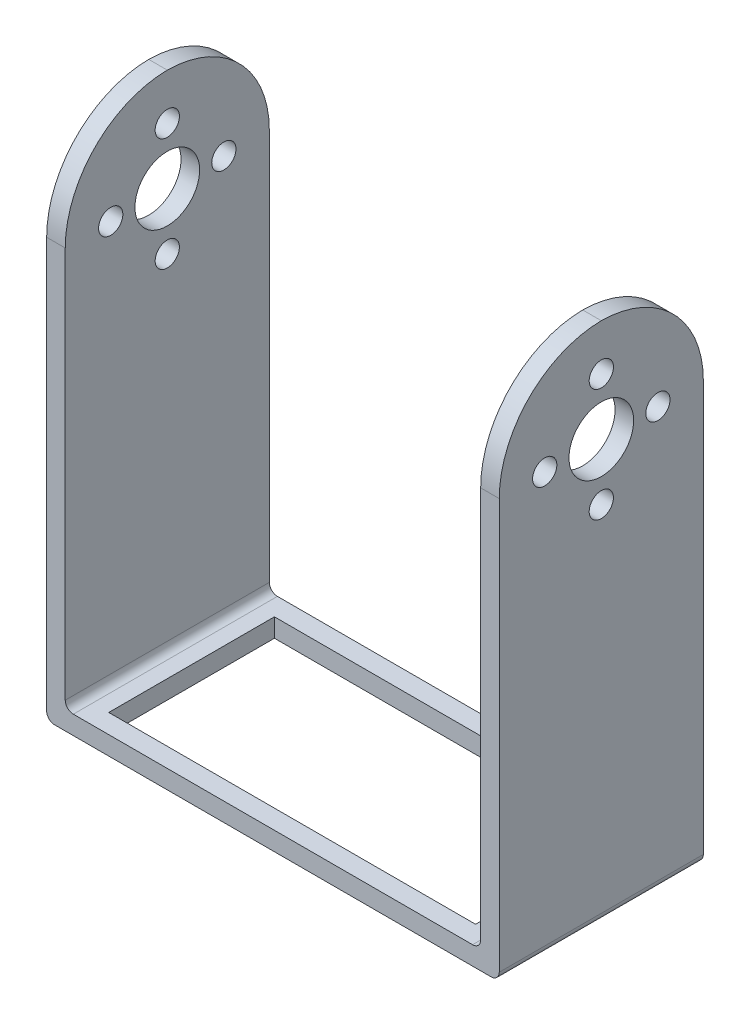
SolidWorks part; units mm, degrees
ref_plane "Front Plane" through (0, 0, 0) normal (0, 0, 1) x (1, 0, 0)
ref_plane "Top Plane" through (0, 0, 0) normal (0, 1, 0) x (1, 0, 0)
ref_plane "Right Plane" through (0, 0, 0) normal (1, 0, 0) x (0, 0, -1)
sketch "Sketch1" plane through (0, 0, 0) normal (0, 0, 1) x (1, 0, 0)
  line L1 (-28, 32.25) -> (28, 32.25)
  line L2 (-28, 32.25) -> (-28, -32.25)
  line L3 (-28, -32.25) -> (28, -32.25)
  line L4 (28, 32.25) -> (28, -32.25)
  line L5 (-28, 32.25) -> (28, -32.25) construction
  line L6 (-28, -32.25) -> (28, 32.25) construction
  point P0 (0, 0)
  dimension "D1" = 56
  dimension "D2" = 64.5
extrude "Boss-Extrude1" add sketch "Sketch1" along normal blind 25.25
sketch "Sketch2" plane through (0, 0, 25.25) normal (0, 0, 1) x (1, 0, 0)
  line L0 (28, 32.25) -> (-28, 32.25) construction
  line L1 (-25.7, 32.25) -> (25.7, 32.25)
  line L2 (-25.7, 32.25) -> (-25.7, -29.95)
  line L3 (-25.7, -29.95) -> (25.7, -29.95)
  line L4 (25.7, 32.25) -> (25.7, -29.95)
  line L5 (-28, 32.25) -> (-28, -32.25) construction
  line L6 (-28, -32.25) -> (28, -32.25) construction
  line L7 (28, -32.25) -> (28, 32.25) construction
  dimension "D1" = 2.3
  dimension "D2" = 2.3
  dimension "D3" = 2.3
extrude "Cut-Extrude1" cut sketch "Sketch2" against normal through all
fillet "Fillet1" radius 1 4 edges at (-28, -32.25, 12.625) (28, -32.25, 12.625) (25.7, -29.95, 12.625) (-25.7, -29.95, 12.625)
fillet "Fillet3" radius 12.75 4 edges at (-26.85, 32.25, 25.25) (26.85, 32.25, 25.25) (-26.85, 32.25, 0) (26.85, 32.25, 0)
sketch "Sketch4" plane through (0, -32.25, 0) normal (0, -1, 0) x (1, 0, 0)
  line L3 (-22.6935, 22.875) -> (22.6935, 22.875)
  line L5 (-22.6935, 22.875) -> (-22.6935, 2.375)
  line L7 (-22.6935, 2.375) -> (22.6935, 2.375)
  line L8 (22.6935, 22.875) -> (22.6935, 2.375)
  point P2 (0, 12.625)
extrude "Cut-Extrude3" cut sketch "Sketch4" against normal through all
sketch "Sketch5" plane through (-28, 0, 0) normal (-1, 0, 0) x (0, 0, 1)
  line L2 (0, 19.5) -> (0, -31.25) construction
  circle A0 centre (12.625, 19.5494) radius 4
  circle A1 centre (12.625, 26.5494) radius 1.5
  circle A2 centre (19.625, 19.5494) radius 1.5
  circle A3 centre (12.625, 12.5494) radius 1.5
  circle A4 centre (5.625, 19.5494) radius 1.5
  dimension "D1" = 8
  dimension "D3" = 3
  dimension "D2" = 12.625
  dimension "D4" = 7
  dimension "D5" = 7
  dimension "D6" = 7
  dimension "D7" = 7
  dimension "D8" = 12.7
extrude "Cut-Extrude4" cut sketch "Sketch5" against normal through all
